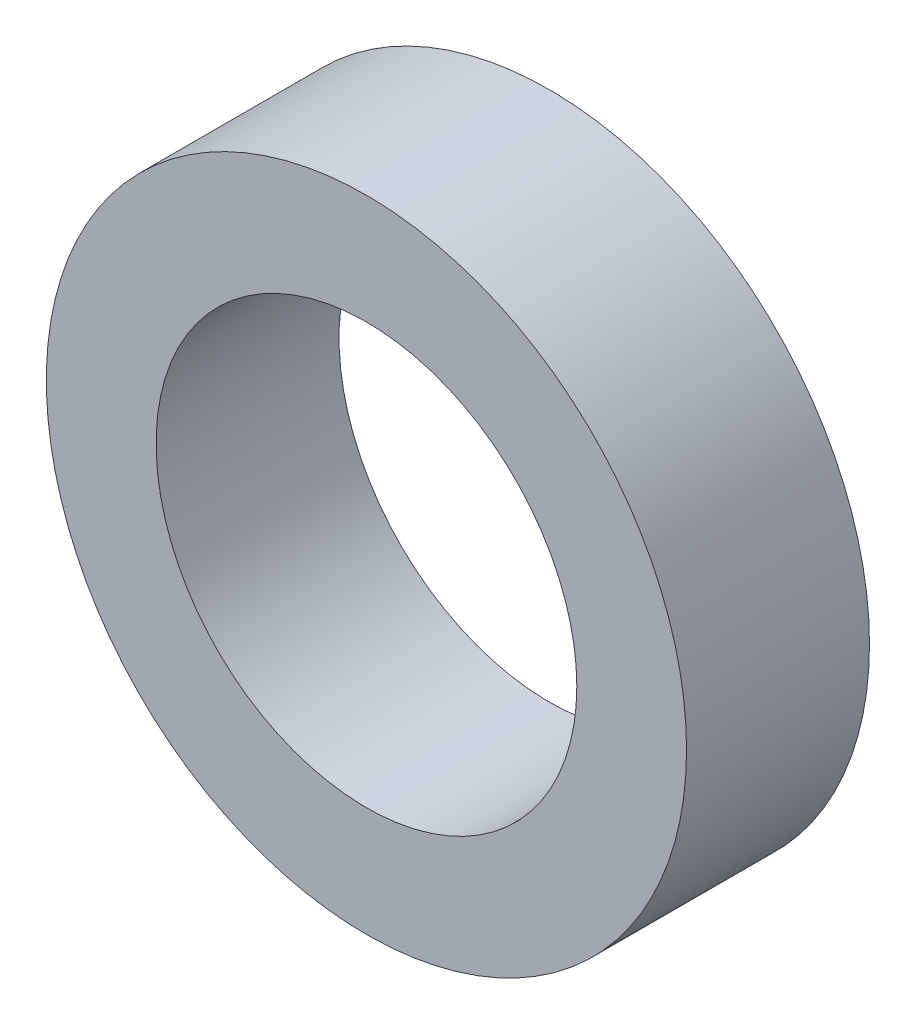
SolidWorks part; units mm, degrees
ref_plane "Plane1" through (0, 0, 0) normal (0, 0, 1) x (1, 0, 0)
ref_plane "Plane2" through (0, 0, 0) normal (0, 1, 0) x (1, 0, 0)
ref_plane "Plane3" through (0, 0, 0) normal (1, 0, 0) x (0, 0, -1)
sketch "Sketch1" plane through (0, 0, 0) normal (0, 0, 1) x (1, 0, 0)
  circle A0 centre (0, 0) radius 29.21
  circle A1 centre (0, 0) radius 44.45
extrude "BasePipeXXS" add sketch "Sketch1" along normal mid plane 25.4
